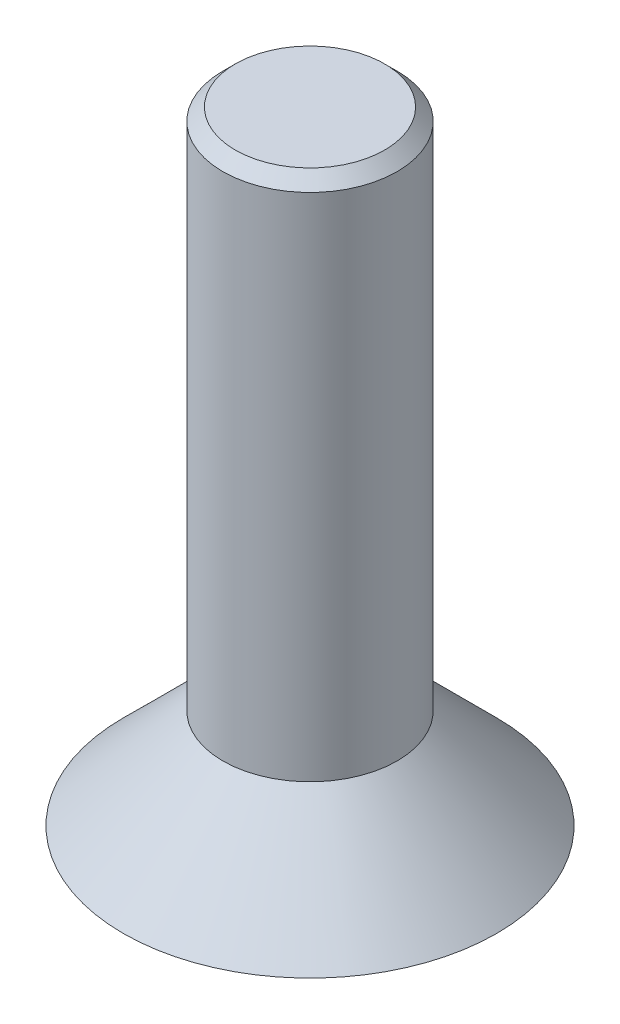
SolidWorks part; units mm, degrees
material "铸造合金钢"
ref_plane "前视基准面" through (0, 0, 0) normal (0, 0, 1) x (1, 0, 0)
ref_plane "上视基准面" through (0, 0, 0) normal (0, 1, 0) x (1, 0, 0)
ref_plane "右视基准面" through (0, 0, 0) normal (1, 0, 0) x (0, 0, -1)
sketch "草图1" plane through (0, 0, 0) normal (0, 1, 0) x (1, 0, 0)
  line L1 (0, -1.1547) -> (1, -0.5774)
  line L2 (1, -0.5774) -> (1, 0.5774)
  line L3 (1, 0.5774) -> (0, 1.1547)
  line L4 (0, 1.1547) -> (-1, 0.5774)
  line L5 (-1, 0.5774) -> (-1, -0.5774)
  line L6 (-1, -0.5774) -> (0, -1.1547)
  circle A0 centre (0, 0) radius 3
  circle A1 centre (0, 0) radius 1 construction
  dimension "D1" = 6
  dimension "D2" = 2
extrude "凸台-拉伸1" add sketch "草图1" along normal blind 1.6
chamfer "倒角1" distance 1.6 angle 45 1 edges at (0, 1.6, 3)
sketch "草图2" plane through (0, 1.6, 0) normal (0, 1, 0) x (1, 0, 0)
  circle A0 centre (0, 0) radius 1.4
  dimension "D1" = 2.8
extrude "凸台-拉伸2" add sketch "草图2" along normal blind 8.4
chamfer "倒角2" distance 0.2 angle 45 1 edges at (0, 10, 1.4)
